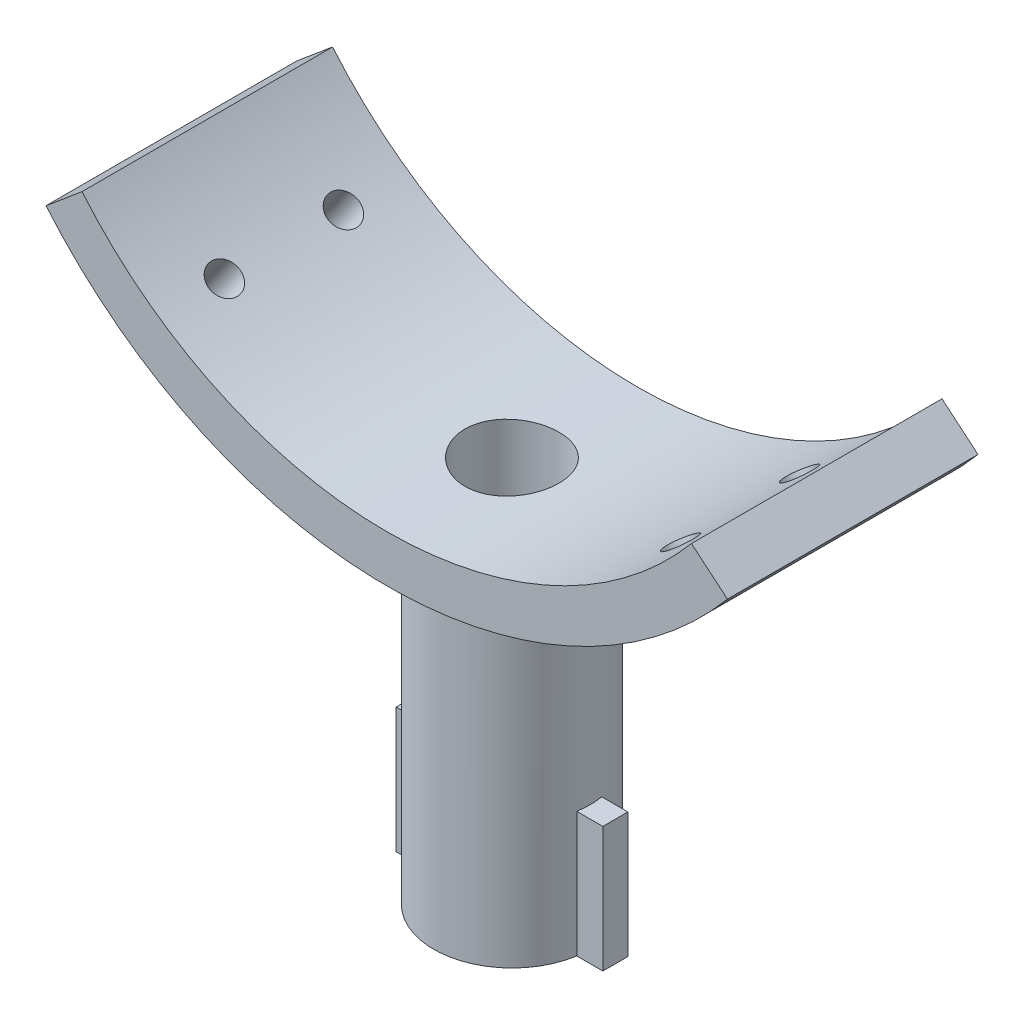
SolidWorks part; units mm, degrees
ref_plane "Front Plane" through (0, 0, 0) normal (0, 0, 1) x (1, 0, 0)
ref_plane "Top Plane" through (0, 0, 0) normal (0, 1, 0) x (1, 0, 0)
ref_plane "Right Plane" through (0, 0, 0) normal (1, 0, 0) x (0, 0, -1)
sketch "Sketch1" plane through (0, 0, 0) normal (0, 0, 1) x (1, 0, 0)
  line L0 (0, 31.2519) -> (0, -31.2519) construction
  line L1 (0, 0) -> (-21.7557, -18.2552) construction
  line L2 (0, 0) -> (21.7557, -18.2552) construction
  line L3 (21.7557, -18.2552) -> (19.4575, -16.3268)
  line L4 (-21.7557, -18.2552) -> (-19.4575, -16.3268)
  arc A0 (-19.4575, -16.3268) -> (19.4575, -16.3268) centre (0, 0) ccw
  arc A1 (-21.7557, -18.2552) -> (21.7557, -18.2552) centre (0, 0) ccw
  circle A2 centre (0, 0) radius 28.4 construction
  circle A3 centre (0, 0) radius 25.4 construction
  point P3 (-12.8738, -4.6857)
  point P8 (0, 0)
  dimension "D1" = 50.8
  dimension "D3" = 50
  dimension "D2" = 3
extrude "Boss-Extrude1" add sketch "Sketch1" along normal mid plane 16
ref_plane "Plane1" through (0, -50, 0) normal (0, 1, 0) x (1, 0, 0)
sketch "Sketch2" plane through (0, -50, 0) normal (0, 1, 0) x (1, 0, 0)
  circle A0 centre (0, 0) radius 5
  dimension "D1" = 10
extrude "Boss-Extrude2" add sketch "Sketch2" along normal up to surface (21.6 mm away) up to face at (0, -23.3276, 0)
sketch "Sketch3" plane through (0, -50, 0) normal (0, -1, 0) x (1, 0, 0)
  circle A0 centre (0, 0) radius 3
  circle A1 centre (0, 0) radius 5 construction
  circle A2 centre (0, 0) radius 5 construction
  dimension "D1" = 2
extrude "Cut-Extrude1" cut sketch "Sketch3" against normal through all
sketch "Sketch4" plane through (0, -50, 0) normal (0, -1, 0) x (1, 0, 0)
  line L0 (-6.6, 0) -> (6.6, 0) construction
  line L5 (-6.6, 0.8) -> (-4.9356, 0.8)
  line L6 (-6.6, 0.8) -> (-6.6, -0.8)
  line L7 (-6.6, -0.8) -> (-4.9356, -0.8)
  line L8 (6.6, 0.8) -> (6.6, -0.8)
  line L9 (0, 12.2903) -> (0, -12.2903) construction
  line L10 (4.9356, 0.8) -> (6.6, 0.8)
  line L11 (4.9356, -0.8) -> (6.6, -0.8)
  circle A0 centre (0, 0) radius 5 construction
  arc A1 (-4.9356, 0.8) -> (-4.9356, -0.8) centre (0, 0) ccw
  arc A2 (4.9356, -0.8) -> (4.9356, 0.8) centre (0, 0) ccw
  point P10 (0, 0)
  point P11 (0, 0)
  point P12 (6.6, 0)
  point P13 (0, 0)
  point P16 (0, 0)
  point P18 (0, 0)
  point P20 (5, 0)
  dimension "D1" = 1.6
  dimension "D2" = 1.6
extrude "Boss-Extrude3" add sketch "Sketch4" against normal blind 8
sketch "Sketch5" plane through (0, 0, 0) normal (0, 0, 1) x (1, 0, 0)
  line L0 (0, 0) -> (16.2896, -23.2639) construction
  line L1 (0, 14.0723) -> (0, -38.9472) construction
  line L2 (0, 0) -> (-16.2896, -23.2639) construction
  arc A0 (-21.7557, -18.2552) -> (21.7557, -18.2552) centre (0, 0) ccw construction
  dimension "D1" = 35
ref_plane "Plane3" through (16.2896, -23.2639, 0) normal (0.5736, -0.8192, 0) x (-0.8192, -0.5736, 0)
sketch "Sketch13" plane through (16.2896, -23.2639, 0) normal (0.5736, -0.8192, 0) x (-0.8192, -0.5736, 0)
  line L0 (-17.4465, 0) -> (25.4678, 0) construction
  circle A1 centre (0, 3.8) radius 1
  circle A2 centre (0, -3.8) radius 1
  point P5 (0, 0)
  point P6 (0, 0)
  dimension "D1" = 2
  dimension "D2" = 3.8
extrude "Cut-Extrude2" cut sketch "Sketch13" against normal through all
mirror "Mirror1" about plane through (0, 0, 0) normal (1, 0, 0) of "Cut-Extrude2"
